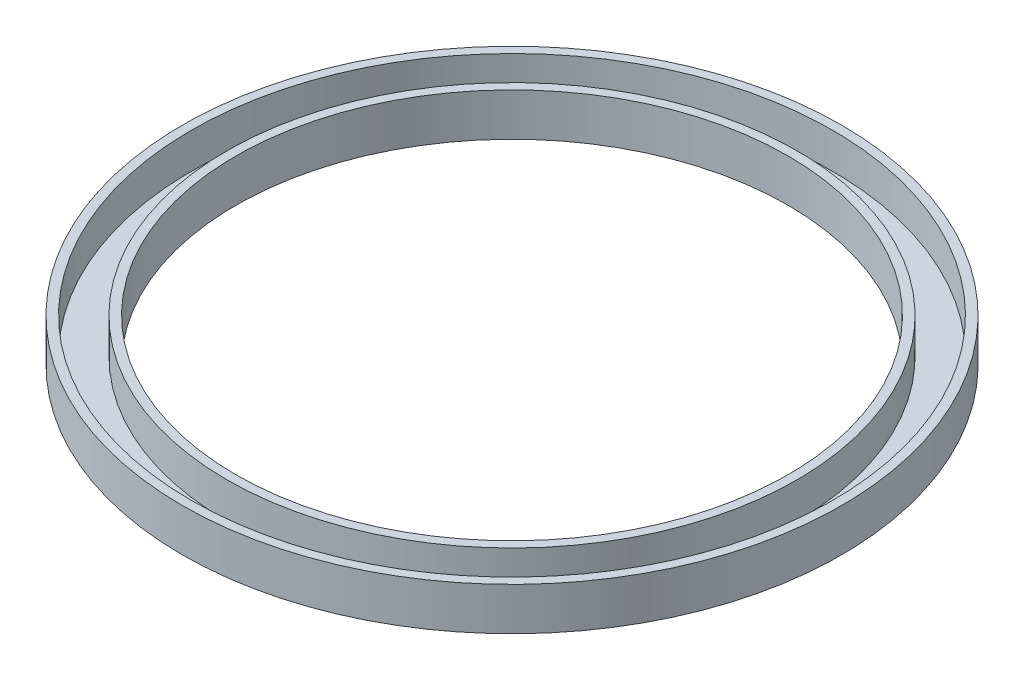
SolidWorks part; units mm, degrees
ref_plane "前视基准面" through (0, 0, 0) normal (0, 0, 1) x (1, 0, 0)
ref_plane "上视基准面" through (0, 0, 0) normal (0, 1, 0) x (1, 0, 0)
ref_plane "右视基准面" through (0, 0, 0) normal (1, 0, 0) x (0, 0, -1)
other "Configuration Table"
sketch "草图1" plane through (0, 0, 0) normal (0, 1, 0) x (1, 0, 0)
  circle A0 centre (0, 0) radius 80
  circle A1 centre (0, 0) radius 90
  circle A2 centre (0, 0) radius 77.5
  circle A3 centre (0, 0) radius 92.5
  dimension "D1" = 180
  dimension "D2" = 160
  dimension "D3" = 155
  dimension "D4" = 185
extrude "凸台-拉伸1" add sketch "草图1" along normal blind 2 contours A1 A0 region at (-87.4544, 0, 0)
extrude "凸台-拉伸2" add sketch "草图1<3>" along normal blind 12 contours A3 A1 | A0 A2 region at (-77.7373, 0, 0) region at (-92.2384, 0, 0)
sketch "草图1<3>" plane through (0, 0, 0) normal (0, 1, 0) x (1, 0, 0) same geometry as "草图1"
